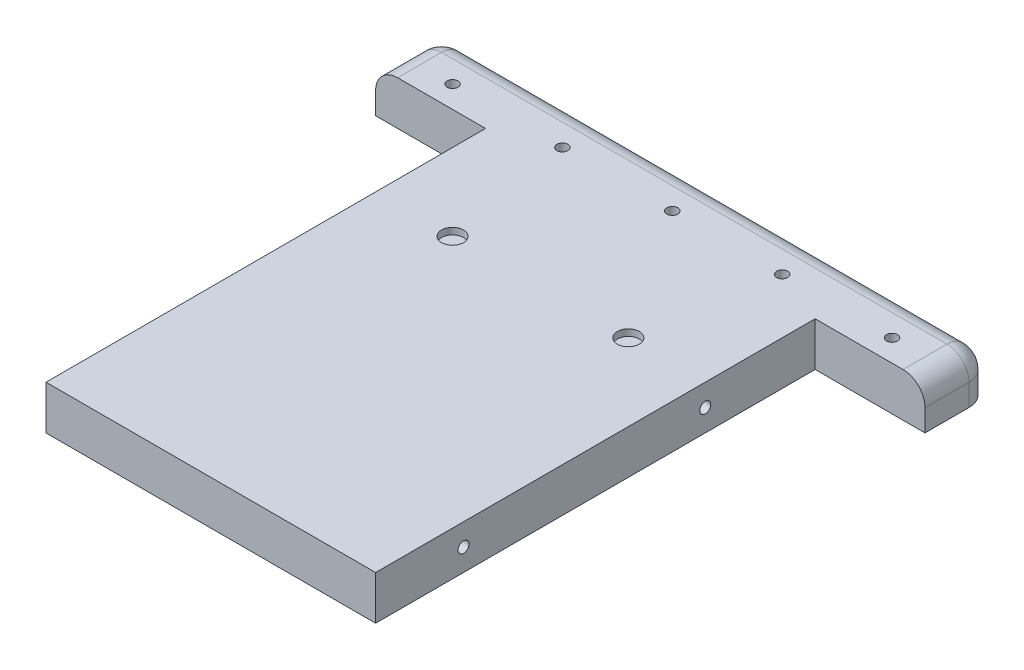
SolidWorks part; units mm, degrees
ref_plane "Front Plane" through (0, 0, 0) normal (0, 0, 1) x (1, 0, 0)
ref_plane "Top Plane" through (0, 0, 0) normal (0, 1, 0) x (1, 0, 0)
ref_plane "Right Plane" through (0, 0, 0) normal (1, 0, 0) x (0, 0, -1)
sketch "Sketch1" plane through (0, 0, 0) normal (0, 1, 0) x (1, 0, 0)
  line L0 (-75, -100) -> (75, -100)
  line L1 (75, -100) -> (75, 100)
  line L2 (75, 100) -> (125, 100)
  line L3 (125, 100) -> (125, 130)
  line L4 (125, 130) -> (-125, 130)
  line L5 (-125, 130) -> (-125, 100)
  line L6 (-125, 100) -> (-75, 100)
  line L7 (-75, 100) -> (-75, -100)
  point P7 (0, -100)
  point P9 (-75, 0)
  dimension "D1" = 250
  dimension "D2" = 30
  dimension "D3" = 150
  dimension "D4" = 200
extrude "Boss-Extrude1" add sketch "Sketch1" along normal blind 20
sketch "Sketch2" plane through (-75, 0, 0) normal (-1, 0, 0) x (0, 0, 1)
  line L0 (100, 20) -> (100, 0) construction
  circle A0 centre (60, 10) radius 2.5
  circle A1 centre (-50, 10) radius 2.5
  point P6 (100, 10)
  dimension "D1" = 5
  dimension "D2" = 40
  dimension "D3" = 110
extrude "Cut-Extrude1" cut sketch "Sketch2" against normal through all
sketch "Sketch4" plane through (0, 0, 0) normal (0, -1, 0) x (1, 0, 0)
  line L0 (-125, -115) -> (125, -115) construction
  line L1 (-125, -130) -> (-125, -100) construction
  line L2 (125, -100) -> (125, -130) construction
  line L3 (0, -11) -> (0, 11) construction
  circle A0 centre (-100, -115) radius 2.5
  circle A1 centre (-50, -115) radius 2.5
  circle A2 centre (0, -115) radius 2.5
  circle A3 centre (50, -115) radius 2.5
  circle A4 centre (100, -115) radius 2.5
  dimension "D1" = 5
  dimension "D2" = 25
  dimension "D3" = 50
extrude "Cut-Extrude2" cut sketch "Sketch4" against normal blind 5
fillet "Fillet1" radius 10 2 edges at (125, 10, -130) (-125, 10, -130)
fillet "Fillet2" radius 10 5 edges at (125, 20, -110) (122.0711, 20, -127.0711) (-125, 20, -110) (-122.0711, 20, -127.0711) (0, 20, -130)
sketch "Sketch6" plane through (0, 20, 0) normal (0, 1, 0) x (1, 0, 0)
  line L0 (115, 110) -> (-115, 110) construction
  line L1 (115, 100) -> (115, 120) construction
  line L2 (-115, 120) -> (-115, 100) construction
  line L3 (0, -11) -> (0, 11) construction
  circle A0 centre (0, 110) radius 2.5
  circle A1 centre (50, 110) radius 2.5
  circle A2 centre (100, 110) radius 2.5
  circle A3 centre (-50, 110) radius 2.5
  circle A4 centre (-100, 110) radius 2.5
  dimension "D1" = 5
  dimension "D2" = 50
  dimension "D3" = 50
extrude "Cut-Extrude3" cut sketch "Sketch6" against normal blind 5
sketch "Sketch7" plane through (0, 20, 0) normal (0, 1, 0) x (1, 0, 0)
  line L0 (-40, -20) -> (40, -20) construction
  line L1 (-75, -100) -> (75, -100) construction
  line L2 (0, -11) -> (0, 11) construction
  line L3 (115, 100) -> (115, 120) construction
  line L4 (75, 100) -> (115, 100) construction
  text T0 "<b>SLRC 2021</b>" font "Century Gothic" height 12
  point P5 (0, -20)
  dimension "D1" = 80
  dimension "D2" = 80
  dimension "D3" = 137.9026
  dimension "D4" = 117.9001
extrude "Cut-Extrude4" [suppressed] cut sketch "Sketch7" against normal blind 3
sketch "Sketch8" plane through (0, 20, 0) normal (0, 1, 0) x (1, 0, 0)
  line L0 (-75, 100) -> (-75, -100) construction
  line L1 (-75, -100) -> (75, -100) construction
  line L2 (0, -11) -> (0, 11) construction
  circle A0 centre (-40, 50) radius 5
  circle A1 centre (40, 50) radius 5
  dimension "D1" = 10
  dimension "D2" = 35
  dimension "D3" = 150
extrude "Cut-Extrude5" cut sketch "Sketch8" against normal blind 3
